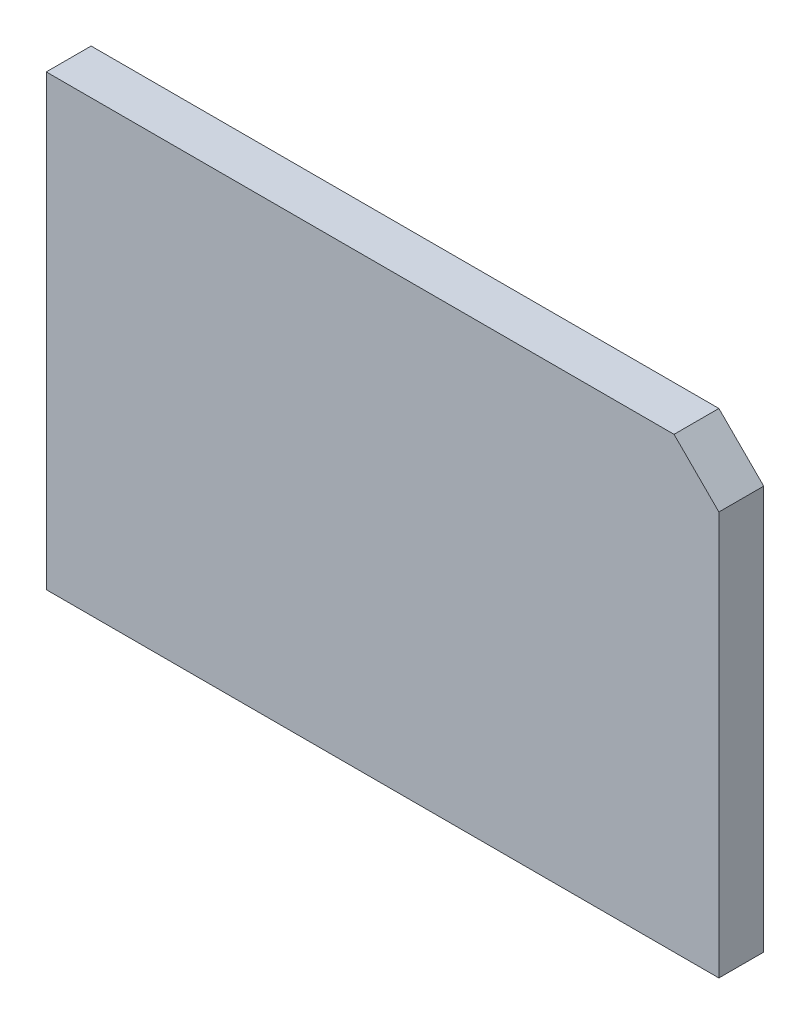
SolidWorks part; units mm, degrees
ref_plane "Front Plane" through (0, 0, 0) normal (0, 0, 1) x (1, 0, 0)
ref_plane "Top Plane" through (0, 0, 0) normal (0, 1, 0) x (1, 0, 0)
ref_plane "Right Plane" through (0, 0, 0) normal (1, 0, 0) x (0, 0, -1)
sketch "Sketch1" plane through (0, 0, 0) normal (0, 0, 1) x (1, 0, 0)
  line L1 (-750, 500) -> (750, 500)
  line L2 (-750, 500) -> (-750, -500)
  line L3 (-750, -500) -> (750, -500)
  line L4 (750, 500) -> (750, -500)
  dimension "table_width" = 1000
  dimension "table_length" = 1500
  dimension "D1" = 750
  dimension "D2" = 500
extrude "Boss-Extrude1" add sketch "Sketch1" against normal blind 100
sketch "Sketch2" plane through (0, 0, 0) normal (0, 0, 1) x (1, 0, 0)
  line L0 (650, 500) -> (750, 400)
  line L1 (750, 500) -> (-750, 500) construction
  line L2 (750, -500) -> (750, 500) construction
  line L3 (750, 400) -> (750, 500)
  line L4 (750, 500) -> (650, 500)
  dimension "D1" = 45
  dimension "D2" = 100
extrude "Cut-Extrude1" cut sketch "Sketch2" against normal blind 200
equation "\"D1@Sketch1\"= \"table_length@Sketch1\" / 2"
equation "\"D2@Sketch1\"=\"table_width@Sketch1\"/2"
